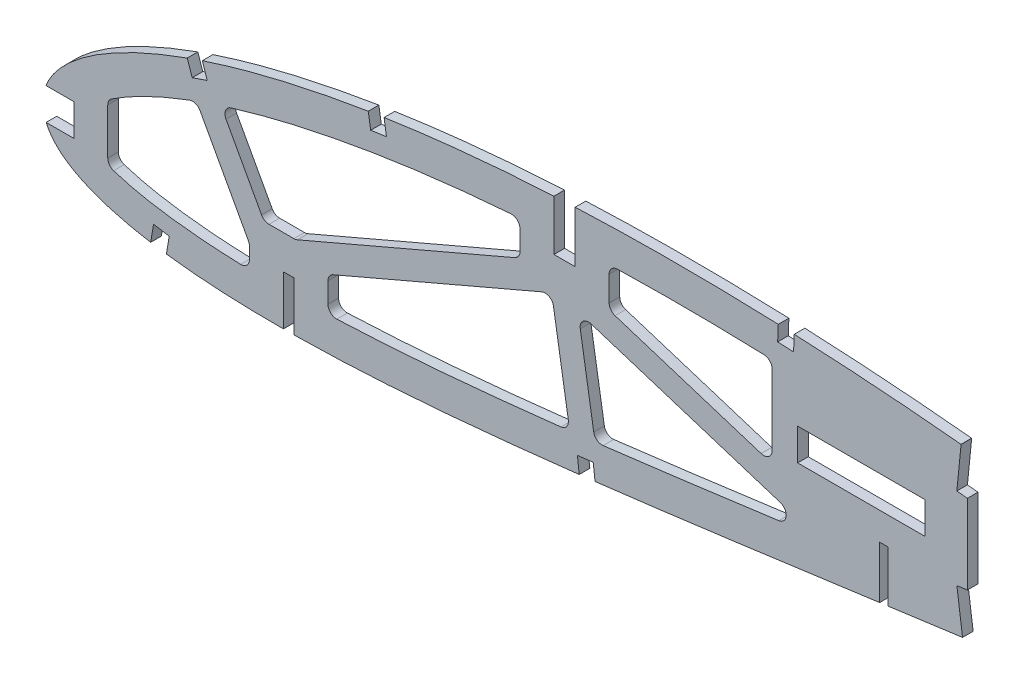
SolidWorks part; units mm, degrees
material "Plywood"
ref_plane "Front Plane" through (0, 0, 0) normal (0, 0, 1) x (1, 0, 0)
ref_plane "Top Plane" through (0, 0, 0) normal (0, 1, 0) x (1, 0, 0)
ref_plane "Right Plane" through (0, 0, 0) normal (1, 0, 0) x (0, 0, -1)
curve "Curve1"
  spline degree 3 poles (452.1031, 0.7048, 0) (452.0685, 0.7262, 0) (451.9301, 0.8117, 0) (451.6183, 1.003, 0) (451.099, 1.3216, 0) (450.372, 1.7653, 0) (449.438, 2.3329, 0) (448.2963, 3.0204, 0) (446.9478, 3.8257, 0) (445.3928, 4.7448, 0) (443.6314, 5.7736, 0) (441.6643, 6.9077, 0) (439.4916, 8.1409, 0) (437.1143, 9.468, 0) (434.5331, 10.8828, 0) (431.7485, 12.3789, 0) (428.7615, 13.9486, 0) (425.5733, 15.5853, 0) (422.1844, 17.2798, 0) (418.5964, 19.0251, 0) (414.8106, 20.8125, 0) (410.8282, 22.6325, 0) (406.6515, 24.4776, 0) (402.2816, 26.3365, 0) (397.7212, 28.201, 0) (392.972, 30.0605, 0) (388.0369, 31.9065, 0) (382.9178, 33.7272, 0) (377.6186, 35.5144, 0) (372.1418, 37.2567, 0) (366.4913, 38.9446, 0) (360.6704, 40.5671, 0) (354.684, 42.1159, 0) (348.5359, 43.5797, 0) (342.2312, 44.9487, 0) (335.775, 46.2147, 0) (329.1727, 47.3651, 0) (322.4425, 48.3989, 0) (315.6929, 49.2588, 0) (308.9571, 50.1023, 0) (302.2314, 50.8946, 0) (295.4235, 51.6533, 0) (288.5399, 52.3742, 0) (281.5875, 53.055, 0) (274.5733, 53.6928, 0) (267.5046, 54.2857, 0) (260.3883, 54.8303, 0) (253.2318, 55.3259, 0) (246.0422, 55.768, 0) (238.8272, 56.1563, 0) (231.5941, 56.4881, 0) (224.3504, 56.7611, 0) (217.1039, 56.9737, 0) (209.862, 57.1238, 0) (202.6326, 57.2105, 0) (195.4232, 57.2315, 0) (188.2416, 57.1863, 0) (181.0954, 57.0734, 0) (173.9924, 56.8912, 0) (166.9401, 56.6395, 0) (159.9462, 56.3182, 0) (153.0184, 55.9248, 0) (146.164, 55.4618, 0) (139.3909, 54.9271, 0) (132.7063, 54.3206, 0) (126.1174, 53.645, 0) (119.6314, 52.8983, 0) (113.2554, 52.0826, 0) (106.9962, 51.1996, 0) (100.8609, 50.2488, 0) (94.8561, 49.2329, 0) (88.9882, 48.153, 0) (83.2635, 47.0122, 0) (77.6882, 45.8109, 0) (72.2682, 44.5525, 0) (67.0092, 43.2395, 0) (61.9167, 41.874, 0) (56.9959, 40.4594, 0) (52.2519, 38.999, 0) (47.6902, 37.4943, 0) (43.3141, 35.951, 0) (39.1291, 34.3702, 0) (35.1384, 32.7568, 0) (31.3466, 31.113, 0) (27.7567, 29.4439, 0) (24.3726, 27.7512, 0) (21.1967, 26.0397, 0) (18.2324, 24.3122, 0) (15.4823, 22.5717, 0) (12.9477, 20.8227, 0) (10.632, 19.0664, 0) (8.5361, 17.307, 0) (6.6613, 15.5474, 0) (5.0102, 13.7886, 0) (3.5829, 12.0339, 0) (2.3811, 10.2847, 0) (1.4051, 8.5424, 0) (0.6571, 6.8085, 0) (0.1363, 5.084, 0) (-0.1488, 3.3712, 0) (-0.2197, 1.669, 0) (-0.0731, 0.5555, 0) (0, 0, 0) knots 0 0 0 0 0.000254 0.001015 0.002283 0.004057 0.006331 0.009105 0.012374 0.016134 0.02038 0.025106 0.030306 0.035972 0.0421 0.048678 0.055702 0.06316 0.071046 0.07935 0.088063 0.097176 0.106678 0.116562 0.126814 0.137428 0.148394 0.1597 0.171338 0.183298 0.19557 0.208144 0.221012 0.234162 0.247587 0.261277 0.275223 0.289414 0.303771 0.317689 0.331784 0.34604 0.360444 0.374983 0.38964 0.404403 0.419257 0.434187 0.449177 0.464215 0.479284 0.49437 0.509458 0.524532 0.539579 0.554583 0.56953 0.584403 0.599191 0.613877 0.628447 0.642889 0.657186 0.671326 0.685294 0.699078 0.712665 0.726043 0.739198 0.752118 0.764792 0.777208 0.789356 0.801224 0.812804 0.824083 0.835055 0.84571 0.856038 0.866034 0.875689 0.884998 0.893953 0.902553 0.910789 0.918661 0.926166 0.933303 0.940071 0.946475 0.952518 0.958205 0.963547 0.968557 0.97325 0.977651 0.981787 0.985694 0.989415 0.993001 0.996508 1 1 1 1
curve "Curve2"
  spline degree 3 poles (0, 0, 0) (0.1161, -0.5481, 0) (0.3488, -1.6467, 0) (0.9811, -3.2283, 0) (1.8173, -4.7487, 0) (2.8749, -6.2038, 0) (4.147, -7.5932, 0) (5.6306, -8.9184, 0) (7.3243, -10.1787, 0) (9.226, -11.3735, 0) (11.3328, -12.5041, 0) (13.6425, -13.5697, 0) (16.1528, -14.5701, 0) (18.8611, -15.5039, 0) (21.764, -16.3724, 0) (24.8588, -17.1737, 0) (28.1419, -17.9088, 0) (31.6103, -18.5759, 0) (35.26, -19.1755, 0) (39.0874, -19.7075, 0) (43.0885, -20.172, 0) (47.2594, -20.5682, 0) (51.596, -20.8969, 0) (56.0938, -21.1583, 0) (60.7487, -21.3533, 0) (65.556, -21.481, 0) (70.5112, -21.5436, 0) (75.6096, -21.5419, 0) (80.8464, -21.4754, 0) (86.2171, -21.3479, 0) (91.7164, -21.1586, 0) (97.3395, -20.9096, 0) (103.0813, -20.6036, 0) (108.9365, -20.2416, 0) (114.9002, -19.8251, 0) (120.967, -19.3576, 0) (127.1315, -18.8401, 0) (133.3883, -18.2757, 0) (139.7319, -17.6673, 0) (146.1567, -17.0167, 0) (152.6572, -16.327, 0) (159.2275, -15.6004, 0) (165.862, -14.8409, 0) (172.5546, -14.0497, 0) (179.2998, -13.2315, 0) (186.0911, -12.3877, 0) (192.923, -11.5217, 0) (199.7891, -10.6375, 0) (206.6832, -9.7349, 0) (213.5994, -8.8205, 0) (220.5311, -7.8935, 0) (227.4721, -6.9586, 0) (234.4161, -6.0188, 0) (241.3564, -5.0743, 0) (248.2868, -4.1291, 0) (255.2009, -3.1857, 0) (262.0918, -2.2442, 0) (268.9535, -1.3094, 0) (275.779, -0.3811, 0) (282.5619, 0.5389, 0) (289.2958, 1.4477, 0) (295.9744, 2.3443, 0) (302.5907, 3.228, 0) (309.138, 4.0992, 0) (315.5119, 4.9314, 0) (321.6955, 5.769, 0) (327.7099, 6.4556, 0) (333.6493, 7.0417, 0) (339.52, 7.5222, 0) (345.315, 7.9041, 0) (351.0275, 8.19, 0) (356.6509, 8.3839, 0) (362.1779, 8.4917, 0) (367.6017, 8.516, 0) (372.9148, 8.4647, 0) (378.1105, 8.3417, 0) (383.1813, 8.1528, 0) (388.1203, 7.9042, 0) (392.9205, 7.6027, 0) (397.5745, 7.2527, 0) (402.076, 6.8625, 0) (406.4179, 6.4377, 0) (410.5937, 5.9833, 0) (414.5972, 5.5086, 0) (418.4221, 5.0169, 0) (422.0625, 4.5163, 0) (425.5126, 4.0117, 0) (428.7669, 3.5097, 0) (431.8204, 3.015, 0) (434.6681, 2.5342, 0) (437.3055, 2.0718, 0) (439.7281, 1.6323, 0) (441.9324, 1.2212, 0) (443.9143, 0.8406, 0) (445.6709, 0.4968, 0) (447.199, 0.1913, 0) (448.4964, -0.0716, 0) (449.5609, -0.2909, 0) (450.3908, -0.463, 0) (450.9844, -0.5881, 0) (451.3411, -0.6626, 0) (451.4997, -0.6964, 0) (451.5393, -0.7048, 0) knots 0 0 0 0 0.003638 0.007293 0.011028 0.014901 0.018963 0.023258 0.027821 0.032679 0.037853 0.043362 0.049215 0.055422 0.061989 0.068918 0.076211 0.083868 0.091887 0.100266 0.109 0.118085 0.127515 0.137285 0.147388 0.157816 0.168563 0.179619 0.190977 0.202627 0.21456 0.226767 0.239236 0.251959 0.264924 0.27812 0.291536 0.30516 0.318981 0.332985 0.347163 0.361499 0.375981 0.390597 0.405333 0.420175 0.43511 0.450124 0.465203 0.480333 0.495501 0.51069 0.525887 0.541078 0.556247 0.571382 0.586466 0.601485 0.616424 0.631269 0.646007 0.660621 0.675098 0.689423 0.703582 0.716908 0.730009 0.742952 0.755726 0.76832 0.780724 0.792927 0.804916 0.816679 0.828204 0.839475 0.850481 0.861208 0.871639 0.881763 0.891564 0.901027 0.910139 0.918884 0.927249 0.935221 0.942785 0.949928 0.956638 0.962904 0.968712 0.974054 0.978918 0.983297 0.98718 0.990561 0.993433 0.995791 0.99763 0.998946 0.999737 1 1 1 1
sketch "Sketch1" plane through (0, 0, 0) normal (0, 0, 1) x (1, 0, 0)
  line L24 (435.3301, 0.6787) -> (439.1729, -1.6142)
  line L25 (434.7872, -0.6787) -> (439.1729, -1.6142)
  spline S4 degree 3 poles (0, 0) (0.1118, -0.5277) (0.3359, -1.5856) (0.9447, -3.1085) (1.7499, -4.5725) (2.7683, -5.9736) (3.9931, -7.3115) (5.4217, -8.5876) (7.0526, -9.8011) (8.8837, -10.9516) (10.9124, -12.0402) (13.1363, -13.0663) (15.5535, -14.0296) (18.1613, -14.9287) (20.9565, -15.765) (23.9365, -16.5366) (27.0978, -17.2444) (30.4375, -17.8867) (33.9519, -18.4641) (37.6373, -18.9763) (41.49, -19.4236) (45.5061, -19.8051) (49.6818, -20.1216) (54.0128, -20.3734) (58.4949, -20.5611) (63.1239, -20.6841) (67.8952, -20.7443) (72.8045, -20.7427) (77.847, -20.6787) (83.0184, -20.5559) (88.3137, -20.3736) (93.7282, -20.1339) (99.2569, -19.8392) (104.895, -19.4906) (110.6374, -19.0896) (116.4791, -18.6394) (122.4149, -18.1411) (128.4396, -17.5977) (134.5478, -17.0118) (140.7343, -16.3853) (146.9936, -15.7212) (153.3201, -15.0216) (159.7085, -14.2903) (166.1528, -13.5285) (172.6478, -12.7406) (179.1872, -11.9281) (185.7655, -11.0942) (192.377, -10.2428) (199.0153, -9.3738) (205.6749, -8.4933) (212.3494, -7.6007) (219.0329, -6.7005) (225.7193, -5.7955) (232.4021, -4.886) (239.0753, -3.9759) (245.7329, -3.0675) (252.3682, -2.161) (258.9753, -1.2608) (265.5476, -0.3669) (272.0789, 0.5189) (278.563, 1.394) (284.9937, 2.2573) (291.3645, 3.1082) (297.669, 3.9471) (303.8064, 4.7484) (309.7606, 5.555) (315.5518, 6.2161) (321.2709, 6.7805) (326.9238, 7.2431) (332.5038, 7.6108) (338.0044, 7.8861) (343.4191, 8.0729) (348.7411, 8.1767) (353.9637, 8.2001) (359.0797, 8.1506) (364.0826, 8.0323) (368.9653, 7.8503) (373.7211, 7.6109) (378.3431, 7.3206) (382.8245, 6.9836) (387.159, 6.6079) (391.3398, 6.1989) (395.3607, 5.7613) (399.2157, 5.3043) (402.8986, 4.8308) (406.404, 4.3487) (409.7261, 3.8629) (412.8597, 3.3795) (415.7999, 2.9031) (418.5419, 2.4402) (421.0815, 1.9949) (423.4142, 1.5717) (425.5368, 1.1759) (427.445, 0.8095) (429.1365, 0.4784) (430.6079, 0.1842) (431.8572, -0.0689) (432.8822, -0.2801) (433.6813, -0.4458) (434.2529, -0.5663) (434.5964, -0.638) (434.749, -0.6706) (434.7872, -0.6787) knots 0 0 0 0 0.003638 0.007293 0.011028 0.014901 0.018963 0.023258 0.027821 0.032679 0.037853 0.043362 0.049215 0.055422 0.061989 0.068918 0.076211 0.083868 0.091887 0.100266 0.109 0.118085 0.127515 0.137285 0.147388 0.157816 0.168563 0.179619 0.190977 0.202627 0.21456 0.226767 0.239236 0.251959 0.264924 0.27812 0.291536 0.30516 0.318981 0.332985 0.347163 0.361499 0.375981 0.390597 0.405333 0.420175 0.43511 0.450124 0.465203 0.480333 0.495501 0.51069 0.525887 0.541078 0.556247 0.571382 0.586466 0.601485 0.616424 0.631269 0.646007 0.660621 0.675098 0.689423 0.703582 0.716908 0.730009 0.742952 0.755726 0.76832 0.780724 0.792927 0.804916 0.816679 0.828204 0.839475 0.850481 0.861208 0.871639 0.881763 0.891564 0.901027 0.910139 0.918884 0.927249 0.935221 0.942785 0.949928 0.956638 0.962904 0.968712 0.974054 0.978918 0.983297 0.98718 0.990561 0.993433 0.995791 0.99763 0.998946 0.999737 1 1 1 1
  spline S5 degree 3 poles (435.3301, 0.6787) (435.2968, 0.6993) (435.1635, 0.7816) (434.8632, 0.9658) (434.3632, 1.2726) (433.6632, 1.6998) (432.7638, 2.2463) (431.6645, 2.9084) (430.3661, 3.6837) (428.8687, 4.5688) (427.1727, 5.5594) (425.2785, 6.6514) (423.1865, 7.8389) (420.8974, 9.1168) (418.4119, 10.4791) (415.7306, 11.9197) (412.8545, 13.4311) (409.7845, 15.0071) (406.5213, 16.6387) (403.0665, 18.3192) (399.4211, 20.0403) (395.5865, 21.7928) (391.5647, 23.5695) (387.357, 25.3594) (382.9657, 27.1547) (378.3927, 28.9452) (373.6407, 30.7228) (368.7116, 32.4759) (363.609, 34.1968) (358.3353, 35.8745) (352.8945, 37.4998) (347.2896, 39.0621) (341.5252, 40.5534) (335.6052, 41.9629) (329.5344, 43.2811) (323.3177, 44.5002) (316.9603, 45.6079) (310.4799, 46.6033) (303.9807, 47.4313) (297.4948, 48.2435) (291.0186, 49.0064) (284.4633, 49.737) (277.8351, 50.4311) (271.1406, 51.0867) (264.3866, 51.7008) (257.5802, 52.2717) (250.7279, 52.7961) (243.8369, 53.2733) (236.914, 53.699) (229.9667, 54.0729) (223.0019, 54.3924) (216.027, 54.6553) (209.0493, 54.86) (202.0761, 55.0045) (195.1149, 55.088) (188.173, 55.1082) (181.2578, 55.0647) (174.3767, 54.956) (167.5373, 54.7806) (160.7467, 54.5381) (154.0122, 54.2288) (147.3414, 53.85) (140.7414, 53.4041) (134.2195, 52.8893) (127.7829, 52.3053) (121.4385, 51.6548) (115.1931, 50.9357) (109.0536, 50.1503) (103.0266, 49.3001) (97.119, 48.3846) (91.3369, 47.4064) (85.6868, 46.3665) (80.1745, 45.2681) (74.806, 44.1113) (69.5871, 42.8996) (64.5231, 41.6353) (59.6196, 40.3205) (54.8814, 38.9584) (50.3134, 37.5521) (45.9209, 36.1032) (41.7071, 34.6172) (37.6774, 33.0951) (33.8348, 31.5415) (30.1837, 29.9587) (26.7269, 28.3515) (23.4684, 26.7216) (20.4104, 25.0737) (17.5559, 23.4102) (14.9079, 21.7343) (12.4673, 20.0502) (10.2376, 18.359) (8.2194, 16.6649) (6.4142, 14.9706) (4.8244, 13.2771) (3.45, 11.5875) (2.2928, 9.9031) (1.353, 8.2255) (0.6327, 6.5559) (0.1312, 4.8953) (-0.1433, 3.2462) (-0.2116, 1.607) (-0.0704, 0.5349) (0, 0) knots 0 0 0 0 0.000254 0.001015 0.002283 0.004057 0.006331 0.009105 0.012374 0.016134 0.02038 0.025106 0.030306 0.035972 0.0421 0.048678 0.055702 0.06316 0.071046 0.07935 0.088063 0.097176 0.106678 0.116562 0.126814 0.137428 0.148394 0.1597 0.171338 0.183298 0.19557 0.208144 0.221012 0.234162 0.247587 0.261277 0.275223 0.289414 0.303771 0.317689 0.331784 0.34604 0.360444 0.374983 0.38964 0.404403 0.419257 0.434187 0.449177 0.464215 0.479284 0.49437 0.509458 0.524532 0.539579 0.554583 0.56953 0.584403 0.599191 0.613877 0.628447 0.642889 0.657186 0.671326 0.685294 0.699078 0.712665 0.726043 0.739198 0.752118 0.764792 0.777208 0.789356 0.801224 0.812804 0.824083 0.835055 0.84571 0.856038 0.866034 0.875689 0.884998 0.893953 0.902553 0.910789 0.918661 0.926166 0.933303 0.940071 0.946475 0.952518 0.958205 0.963547 0.968557 0.97325 0.977651 0.981787 0.985694 0.989415 0.993001 0.996508 1 1 1 1
extrude "Boss-Extrude1" add sketch "Sketch1" along normal blind 3.175
sketch "Sketch2" plane through (0, 0, 0) normal (0, 0, -1) x (-1, 0, 0)
  line L0 (-252.7944, 13.2215) -> (-250.2544, 13.2215)
  line L1 (-250.2544, -2.1152) -> (-250.2544, -3.9863)
  line L2 (-252.7944, 13.2215) -> (-252.7944, -2.1152)
  line L4 (-250.2544, -3.9863) -> (-252.7944, -3.0508)
  line L5 (-252.7944, -3.0508) -> (-252.7944, -2.1152)
  line L7 (-159.1319, 54.4222) -> (-159.1319, 39.0391)
  line L8 (-159.1319, 39.0391) -> (-152.7819, 39.0391)
  line L9 (-152.7819, 54.4222) -> (-152.7819, 57.6454)
  line L10 (-74.9944, -5.9288) -> (-74.9944, -20.1418)
  line L12 (-152.7819, 57.6454) -> (-159.1319, 55.5409)
  line L13 (-159.1319, 55.5409) -> (-159.1319, 54.4222)
  line L14 (-71.8194, -5.9288) -> (-71.8194, -20.1418)
  line L16 (-74.9944, -5.9288) -> (-71.8194, -5.9288)
  line L17 (-71.8194, -20.1418) -> (-71.8194, -22.1459)
  line L19 (-152.7819, 54.4222) -> (-152.7819, 39.0391)
  line L20 (-71.8194, -22.1459) -> (-74.9944, -20.9764)
  line L21 (-74.9944, -20.9764) -> (-74.9944, -20.1418)
  line L22 (-250.2544, 13.2215) -> (-250.2544, -2.1152)
extrude "Cut-Extrude1" cut sketch "Sketch2" against normal blind 7.62
sketch "Sketch3" plane through (0, 0, 0) normal (0, 0, -1) x (-1, 0, 0)
  circle A1 centre (-292.3838, 26.2554) radius 6.35
extrude "Cut-Extrude2" cut sketch "Sketch3" against normal blind 7.62
sketch "Sketch4" plane through (0, 0, 3.175) normal (0, 0, 1) x (1, 0, 0)
  line L0 (274.6066, 50.6647) -> (273.3497, 38.0281)
  line L1 (274.6066, 50.6647) -> (273.3497, 38.0281)
  line L2 (276.5088, 37.7139) -> (277.7874, 50.3428)
  line L3 (276.5088, 37.7139) -> (277.7874, 50.3428)
  line L4 (278.2022, 1.3477) -> (276.5088, 13.9346)
  line L5 (278.2022, 1.3477) -> (276.5088, 13.9346)
  line L6 (273.3622, 13.5108) -> (275.0576, 0.9245)
  line L7 (273.3622, 13.5108) -> (275.0576, 0.9245)
  line L8 (224.4836, 49.6431) -> (224.6991, 54.396)
  line L9 (224.4836, 49.6431) -> (224.6991, 54.396)
  line L10 (165.0827, -13.6872) -> (164.5226, -8.9534)
  line L11 (165.0827, -13.6872) -> (164.5226, -8.9534)
  line L12 (102.6454, 44.5104) -> (101.9324, 49.2278)
  line L13 (102.6454, 44.5104) -> (101.9324, 49.2278)
  line L14 (36.8388, -18.5812) -> (37.6418, -13.8082)
  line L15 (36.8388, -18.5812) -> (37.6418, -13.8082)
  line L16 (49.0205, 32.2539) -> (47.492, 36.7462)
  line L17 (49.0205, 32.2539) -> (47.492, 36.7462)
  line L18 (9.0835, -2.7147) -> (9.0835, 6.8103)
  line L19 (9.0835, -2.7147) -> (9.0835, 6.8103)
  line L20 (-0.4415, 6.8103) -> (9.0835, 6.8103)
  line L21 (-0.4415, 6.8103) -> (9.0835, 6.8103)
  line L22 (32.9524, -13.0236) -> (32.1659, -17.7312)
  line L23 (32.9524, -13.0236) -> (32.1659, -17.7312)
  line L24 (97.1897, 48.4826) -> (97.9364, 43.7986)
  line L25 (97.1897, 48.4826) -> (97.9364, 43.7986)
  line L26 (159.7931, -9.5131) -> (160.3442, -14.2455)
  line L27 (159.7931, -9.5131) -> (160.3442, -14.2455)
  line L28 (42.9896, 35.1929) -> (44.512, 30.7197)
  line L29 (42.9896, 35.1929) -> (44.512, 30.7197)
  line L30 (-0.4415, -2.7147) -> (9.0835, -2.7147)
  line L31 (-0.4415, -2.7147) -> (9.0835, -2.7147)
  line L32 (219.9134, 54.5992) -> (219.7258, 49.8498)
  line L33 (219.9134, 54.5992) -> (219.7258, 49.8498)
  line L34 (276.5088, 13.9346) -> (276.5088, 37.7139)
  line L35 (273.3497, 38.0281) -> (276.5088, 37.7139)
  line L36 (276.5088, 13.9346) -> (273.3622, 13.5108)
  line L37 (275.0576, 0.9245) -> (278.2022, 1.3477)
  line L38 (219.7258, 49.8498) -> (224.4836, 49.6431)
  line L39 (224.6991, 54.396) -> (219.9134, 54.5992)
  line L40 (159.7931, -9.5131) -> (164.5226, -8.9534)
  line L41 (165.0827, -13.6872) -> (160.3442, -14.2455)
  line L42 (42.9896, 35.1929) -> (47.492, 36.7462)
  line L43 (44.512, 30.7197) -> (49.0205, 32.2539)
  line L44 (97.1897, 48.4826) -> (101.9324, 49.2278)
  line L45 (102.6454, 44.5104) -> (97.9364, 43.7986)
  line L46 (-0.4415, 6.8103) -> (-0.4415, -2.7147)
  line L47 (32.9524, -13.0236) -> (37.6418, -13.8082)
  line L48 (36.8388, -18.5812) -> (32.1659, -17.7312)
  line L49 (277.7874, 50.3428) -> (274.6066, 50.6647)
  line L50 (275.0576, 0.9245) -> (275.0576, -18.8331)
  line L51 (225.7088, 31.0179) -> (263.8088, 31.0179)
  line L52 (225.7088, 31.0179) -> (225.7088, 21.4929)
  line L53 (225.7088, 21.4929) -> (263.8088, 21.4929)
  line L54 (263.8088, 31.0179) -> (263.8088, 21.4929)
  line L55 (446.0862, 59.9441) -> (446.0862, -18.8331)
  line L56 (446.0862, -18.8331) -> (275.0576, -18.8331)
  line L57 (274.6066, 50.6647) -> (274.6066, 59.9441)
  line L58 (274.6066, 59.9441) -> (446.0862, 59.9441)
  line L59 (32.1659, -17.7312) -> (31.5691, -21.3035)
  line L60 (31.5691, -21.3035) -> (36.2028, -22.0776)
  line L61 (36.2028, -22.0776) -> (36.8388, -18.5812)
  circle A0 centre (292.3838, 26.2554) radius 6.35 construction
  circle A1 centre (292.3838, 26.2554) radius 6.35
  point P40 (263.8088, 26.2554)
  dimension "D1" = 9.525
  dimension "D2" = 38.1
  dimension "D3" = 12.7
extrude "Cut-Extrude3" cut sketch "Sketch4" against normal through all contours L31 L19 L21 | L29 L43 L17 | L48 L15 L47 L23 | L45 L13 L25 | L40 L27 L11 | L33 L38 L9 | L54 L51 L52 L53 | L3 L49 L1 L35 | L3 L34 L5 | L7 L37 L5 L36 | L60 L61 L59 | L61 L48 L59 region at (275.5637, 44.1947, 3.175) region at (361.7755, 20.4803, 3.175) region at (275.7826, 7.4301, 3.175) region at (222.206, 52.1243, 3.175) region at (162.4359, -11.6005, 3.175) region at (99.9278, 46.5083, 3.175) region at (34.9052, -15.7866, 3.175) region at (34.1874, -19.9188, 3.175) region at (46.0051, 33.7288, 3.175) region at (4.321, 2.0478, 3.175) region at (244.7588, 26.2554, 3.175)
sketch "Sketch5" plane through (0, 0, 3.175) normal (0, 0, 1) x (1, 0, 0)
  line L0 (0.7643, 6.8103) -> (9.0835, 6.8103) construction
  line L1 (0.7643, 6.8103) -> (9.0835, 6.8103) construction
  line L2 (0.803, -2.7147) -> (9.0835, -2.7147) construction
  line L3 (0.803, -2.7147) -> (9.0835, -2.7147) construction
  line L4 (273.3622, 13.5108) -> (275.0576, 0.9245) construction
  line L5 (273.3622, 13.5108) -> (275.0576, 0.9245) construction
  line L6 (274.6066, 50.6647) -> (273.3497, 38.0281) construction
  line L7 (274.6066, 50.6647) -> (273.3497, 38.0281) construction
  line L8 (19.2435, 12.3749) -> (19.2435, -4.5391)
  line L9 (9.0835, -2.7147) -> (9.0835, 6.8103) construction
  line L10 (61.6594, 4.2312) -> (46.7663, 31.4868) construction
  line L11 (44.512, 30.7197) -> (49.0205, 32.2539) construction
  line L12 (85.1544, 4.2312) -> (142.6219, 28.8791) construction
  line L13 (169.2919, 28.8791) -> (240.0944, 6.4173) construction
  line L14 (155.9569, 28.8791) -> (162.1578, -9.2332) construction
  line L15 (159.7931, -9.5131) -> (164.5226, -8.9534) construction
  line L16 (66.0011, 4.2312) -> (50.1097, 33.3137)
  line L17 (85.1544, 0.0856) -> (152.2877, 28.8791)
  line L18 (152.1093, 28.8026) -> (158.3973, -9.8451)
  line L19 (159.9871, 27.8339) -> (238.9423, 2.7857)
  line L20 (61.6594, -3.7144) -> (43.4229, 29.6599)
  line L21 (75.4887, 4.2312) -> (142.6219, 33.0248)
  line L22 (159.7175, 29.4909) -> (165.9184, -8.6214)
  line L23 (169.2919, 32.8762) -> (241.2466, 10.049)
  line L24 (65.0029, 6.0582) -> (50.1097, 33.3137) construction
  line L25 (58.316, 2.4043) -> (43.4229, 29.6599) construction
  line L26 (83.6526, 7.7327) -> (141.1201, 32.3806) construction
  line L27 (86.6562, 0.7297) -> (144.1237, 25.3776) construction
  line L28 (152.1964, 28.2673) -> (158.3973, -9.8451) construction
  line L29 (168.1398, 25.2475) -> (238.9423, 2.7857) construction
  line L30 (170.4441, 32.5107) -> (241.2466, 10.049) construction
  line L35 (85.1544, 4.2312) -> (85.1544, -20.7123)
  line L36 (61.6594, 4.2312) -> (85.1544, 4.2312)
  line L37 (61.6594, -20.7377) -> (61.6594, 4.2312)
  line L38 (85.1544, 4.2312) -> (85.1544, -20.7123)
  line L39 (61.6594, 4.2312) -> (85.1544, 4.2312)
  line L40 (61.6594, -10.4783) -> (61.6594, 4.2312)
  line L46 (240.0944, -2.4499) -> (240.0944, 13.2215)
  line L47 (169.2919, 54.4587) -> (169.2919, 28.8791)
  line L48 (169.2919, 28.8791) -> (142.6219, 28.8791)
  line L49 (142.6219, 28.8791) -> (142.6219, 54.1523)
  line L50 (169.2919, 44.6566) -> (169.2919, 28.8791)
  line L51 (169.2919, 28.8791) -> (142.6219, 28.8791)
  line L52 (142.6219, 28.8791) -> (142.6219, 43.3411)
  line L53 (240.0944, 6.4173) -> (240.0944, 13.8729)
  line L62 (263.8088, 38.6379) -> (218.0888, 38.6379)
  line L63 (218.0888, 38.6379) -> (218.0888, 13.8729)
  line L64 (218.0888, 13.8729) -> (263.8088, 13.8729)
  line L66 (218.0888, 44.4072) -> (218.0888, 13.8729)
  line L67 (218.0888, 13.8729) -> (240.0944, 13.8729)
  spline S4 degree 3 poles (1523.9168, 1677.8723) (459.4041, -20.0575) (448.5517, -7.4305) (434.8632, 0.9658) (434.3632, 1.2726) (433.6632, 1.6998) (432.7638, 2.2463) (431.6645, 2.9084) (430.3661, 3.6837) (428.8687, 4.5688) (427.1727, 5.5594) (425.2785, 6.6514) (423.1865, 7.8389) (420.8974, 9.1168) (418.4119, 10.4791) (415.7306, 11.9197) (412.8545, 13.4311) (409.7845, 15.0071) (406.5213, 16.6387) (403.0665, 18.3192) (399.4211, 20.0403) (395.5865, 21.7928) (391.5647, 23.5695) (387.357, 25.3594) (382.9657, 27.1547) (378.3927, 28.9452) (373.6407, 30.7228) (368.7116, 32.4759) (363.609, 34.1968) (358.3353, 35.8745) (352.8945, 37.4998) (347.2896, 39.0621) (341.5252, 40.5534) (335.6052, 41.9629) (329.5344, 43.2811) (323.3177, 44.5002) (316.9603, 45.6079) (310.4799, 46.6033) (303.9807, 47.4313) (297.4948, 48.2435) (291.0186, 49.0064) (284.4633, 49.737) (277.8351, 50.4311) (271.1406, 51.0867) (264.3866, 51.7008) (257.5802, 52.2717) (250.7279, 52.7961) (243.8369, 53.2733) (236.914, 53.699) (229.9667, 54.0729) (223.0019, 54.3924) (216.027, 54.6553) (209.0493, 54.86) (202.0761, 55.0045) (195.1149, 55.088) (188.173, 55.1082) (181.2578, 55.0647) (174.3767, 54.956) (167.5373, 54.7806) (160.7467, 54.5381) (154.0122, 54.2288) (147.3414, 53.85) (140.7414, 53.4041) (134.2195, 52.8893) (127.7829, 52.3053) (121.4385, 51.6548) (115.1931, 50.9357) (109.0536, 50.1503) (103.0266, 49.3001) (97.119, 48.3846) (91.3369, 47.4064) (85.6868, 46.3665) (80.1745, 45.2681) (74.806, 44.1113) (69.5871, 42.8996) (64.5231, 41.6353) (59.6196, 40.3205) (54.8814, 38.9584) (50.3134, 37.5521) (45.9209, 36.1032) (41.7071, 34.6172) (37.6774, 33.0951) (33.8348, 31.5415) (30.1837, 29.9587) (26.7269, 28.3515) (23.4684, 26.7216) (20.4104, 25.0737) (17.5559, 23.4102) (14.9079, 21.7343) (12.4673, 20.0502) (10.2376, 18.359) (8.2194, 16.6649) (6.4142, 14.9706) (4.8244, 13.2771) (3.45, 11.5875) (2.2928, 9.9031) (1.353, 8.2255) (0.6327, 6.5559) (0.1312, 4.8953) (-0.1433, 3.2462) (-1.0017, -17.3492) (61.8716, -33.4146) (-1991.1542, -180.949) knots -0.101807 -0.101807 -0.101807 -0.101807 0.000254 0.001015 0.002283 0.004057 0.006331 0.009105 0.012374 0.016134 0.02038 0.025106 0.030306 0.035972 0.0421 0.048678 0.055702 0.06316 0.071046 0.07935 0.088063 0.097176 0.106678 0.116562 0.126814 0.137428 0.148394 0.1597 0.171338 0.183298 0.19557 0.208144 0.221012 0.234162 0.247587 0.261277 0.275223 0.289414 0.303771 0.317689 0.331784 0.34604 0.360444 0.374983 0.38964 0.404403 0.419257 0.434187 0.449177 0.464215 0.479284 0.49437 0.509458 0.524532 0.539579 0.554583 0.56953 0.584403 0.599191 0.613877 0.628447 0.642889 0.657186 0.671326 0.685294 0.699078 0.712665 0.726043 0.739198 0.752118 0.764792 0.777208 0.789356 0.801224 0.812804 0.824083 0.835055 0.84571 0.856038 0.866034 0.875689 0.884998 0.893953 0.902553 0.910789 0.918661 0.926166 0.933303 0.940071 0.946475 0.952518 0.958205 0.963547 0.968557 0.97325 0.977651 0.981787 0.985694 0.989415 0.993001 0.996508 1.122415 1.122415 1.122415 1.122415 only from (435.3301, 0.6787) to (0, 0) construction
  spline S7 degree 3 poles (-1938.1568, -491.7767) (47.0927, 52.1326) (-6.7204, 16.0645) (0.9447, -3.1085) (1.7499, -4.5725) (2.7683, -5.9736) (3.9931, -7.3115) (5.4217, -8.5876) (7.0526, -9.8011) (8.8837, -10.9516) (10.9124, -12.0402) (13.1363, -13.0663) (15.5535, -14.0296) (18.1613, -14.9287) (20.9565, -15.765) (23.9365, -16.5366) (27.0978, -17.2444) (30.4375, -17.8867) (33.9519, -18.4641) (37.6373, -18.9763) (41.49, -19.4236) (45.5061, -19.8051) (49.6818, -20.1216) (54.0128, -20.3734) (58.4949, -20.5611) (63.1239, -20.6841) (67.8952, -20.7443) (72.8045, -20.7427) (77.847, -20.6787) (83.0184, -20.5559) (88.3137, -20.3736) (93.7282, -20.1339) (99.2569, -19.8392) (104.895, -19.4906) (110.6374, -19.0896) (116.4791, -18.6394) (122.4149, -18.1411) (128.4396, -17.5977) (134.5478, -17.0118) (140.7343, -16.3853) (146.9936, -15.7212) (153.3201, -15.0216) (159.7085, -14.2903) (166.1528, -13.5285) (172.6478, -12.7406) (179.1872, -11.9281) (185.7655, -11.0942) (192.377, -10.2428) (199.0153, -9.3738) (205.6749, -8.4933) (212.3494, -7.6007) (219.0329, -6.7005) (225.7193, -5.7955) (232.4021, -4.886) (239.0753, -3.9759) (245.7329, -3.0675) (252.3682, -2.161) (258.9753, -1.2608) (265.5476, -0.3669) (272.0789, 0.5189) (278.563, 1.394) (284.9937, 2.2573) (291.3645, 3.1082) (297.669, 3.9471) (303.8064, 4.7484) (309.7606, 5.555) (315.5518, 6.2161) (321.2709, 6.7805) (326.9238, 7.2431) (332.5038, 7.6108) (338.0044, 7.8861) (343.4191, 8.0729) (348.7411, 8.1767) (353.9637, 8.2001) (359.0797, 8.1506) (364.0826, 8.0323) (368.9653, 7.8503) (373.7211, 7.6109) (378.3431, 7.3206) (382.8245, 6.9836) (387.159, 6.6079) (391.3398, 6.1989) (395.3607, 5.7613) (399.2157, 5.3043) (402.8986, 4.8308) (406.404, 4.3487) (409.7261, 3.8629) (412.8597, 3.3795) (415.7999, 2.9031) (418.5419, 2.4402) (421.0815, 1.9949) (423.4142, 1.5717) (425.5368, 1.1759) (427.445, 0.8095) (429.1365, 0.4784) (430.6079, 0.1842) (431.8572, -0.0689) (432.8822, -0.2801) (433.6813, -0.4458) (434.2529, -0.5663) (448.3411, -3.5068) (461.0644, -11.9601) (889.5705, 1946.1435) knots -0.127812 -0.127812 -0.127812 -0.127812 0.003638 0.007293 0.011028 0.014901 0.018963 0.023258 0.027821 0.032679 0.037853 0.043362 0.049215 0.055422 0.061989 0.068918 0.076211 0.083868 0.091887 0.100266 0.109 0.118085 0.127515 0.137285 0.147388 0.157816 0.168563 0.179619 0.190977 0.202627 0.21456 0.226767 0.239236 0.251959 0.264924 0.27812 0.291536 0.30516 0.318981 0.332985 0.347163 0.361499 0.375981 0.390597 0.405333 0.420175 0.43511 0.450124 0.465203 0.480333 0.495501 0.51069 0.525887 0.541078 0.556247 0.571382 0.586466 0.601485 0.616424 0.631269 0.646007 0.660621 0.675098 0.689423 0.703582 0.716908 0.730009 0.742952 0.755726 0.76832 0.780724 0.792927 0.804916 0.816679 0.828204 0.839475 0.850481 0.861208 0.871639 0.881763 0.891564 0.901027 0.910139 0.918884 0.927249 0.935221 0.942785 0.949928 0.956638 0.962904 0.968712 0.974054 0.978918 0.983297 0.98718 0.990561 0.993433 0.995791 0.99763 0.998946 0.999737 1.094845 1.094845 1.094845 1.094845 only from (0, 0) to (434.7872, -0.6787) construction
  spline S8 degree 3 poles (0.803, -2.7147) (0.8566, -2.8383) (1.1411, -3.4655) (1.7499, -4.5725) (2.7683, -5.9736) (3.9931, -7.3115) (5.4217, -8.5876) (7.0526, -9.8011) (8.8837, -10.9516) (10.9124, -12.0402) (13.1363, -13.0663) (15.5535, -14.0296) (18.1613, -14.9287) (20.9565, -15.765) (23.9365, -16.5366) (27.0978, -17.2444) (30.4375, -17.8867) (33.9519, -18.4641) (37.6373, -18.9763) (41.49, -19.4236) (45.5061, -19.8051) (49.6818, -20.1216) (54.0128, -20.3734) (58.4949, -20.5611) (63.1239, -20.6841) (67.8952, -20.7443) (72.8045, -20.7427) (77.847, -20.6787) (83.0184, -20.5559) (88.3137, -20.3736) (93.7282, -20.1339) (99.2569, -19.8392) (104.895, -19.4906) (110.6374, -19.0896) (116.4791, -18.6394) (122.4149, -18.1411) (128.4396, -17.5977) (134.5478, -17.0118) (140.7343, -16.3853) (146.9936, -15.7212) (153.3201, -15.0216) (159.7085, -14.2903) (166.1528, -13.5285) (172.6478, -12.7406) (179.1872, -11.9281) (185.7655, -11.0942) (192.377, -10.2428) (199.0153, -9.3738) (205.6749, -8.4933) (212.3494, -7.6007) (219.0329, -6.7005) (225.7193, -5.7955) (232.4021, -4.886) (239.0753, -3.9759) (245.7329, -3.0675) (252.3682, -2.161) (258.9753, -1.2608) (265.5476, -0.3669) (270.9047, 0.3596) (274.0703, 0.7875) (275.0581, 0.9208) knots 0.006385 0.006385 0.006385 0.006385 0.007293 0.011028 0.014901 0.018963 0.023258 0.027821 0.032679 0.037853 0.043362 0.049215 0.055422 0.061989 0.068918 0.076211 0.083868 0.091887 0.100266 0.109 0.118085 0.127515 0.137285 0.147388 0.157816 0.168563 0.179619 0.190977 0.202627 0.21456 0.226767 0.239236 0.251959 0.264924 0.27812 0.291536 0.30516 0.318981 0.332985 0.347163 0.361499 0.375981 0.390597 0.405333 0.420175 0.43511 0.450124 0.465203 0.480333 0.495501 0.51069 0.525887 0.541078 0.556247 0.571382 0.586466 0.601485 0.616424 0.631269 0.638002 0.638002 0.638002 0.638002 construction
  spline S9 degree 3 poles (274.6145, 50.7446) (273.4626, 50.8575) (270.0595, 51.185) (264.3866, 51.7008) (257.5802, 52.2717) (250.7279, 52.7961) (243.8369, 53.2733) (236.914, 53.699) (229.9667, 54.0729) (223.0019, 54.3924) (216.027, 54.6553) (209.0493, 54.86) (202.0761, 55.0045) (195.1149, 55.088) (188.173, 55.1082) (181.2578, 55.0647) (174.3767, 54.956) (167.5373, 54.7806) (160.7467, 54.5381) (154.0122, 54.2288) (147.3414, 53.85) (140.7414, 53.4041) (134.2195, 52.8893) (127.7829, 52.3053) (121.4385, 51.6548) (115.1931, 50.9357) (109.0536, 50.1503) (103.0266, 49.3001) (97.119, 48.3846) (91.3369, 47.4064) (85.6868, 46.3665) (80.1745, 45.2681) (74.806, 44.1113) (69.5871, 42.8996) (64.5231, 41.6353) (59.6196, 40.3205) (54.8814, 38.9584) (50.3134, 37.5521) (45.9209, 36.1032) (41.7071, 34.6172) (37.6774, 33.0951) (33.8348, 31.5415) (30.1837, 29.9587) (26.7269, 28.3515) (23.4684, 26.7216) (20.4104, 25.0737) (17.5559, 23.4102) (14.9079, 21.7343) (12.4673, 20.0502) (10.2376, 18.359) (8.2194, 16.6649) (6.4142, 14.9706) (4.8244, 13.2771) (3.45, 11.5875) (2.2928, 9.9031) (1.404, 8.3167) (0.9441, 7.2755) (0.7643, 6.8103) knots 0.36748 0.36748 0.36748 0.36748 0.374983 0.38964 0.404403 0.419257 0.434187 0.449177 0.464215 0.479284 0.49437 0.509458 0.524532 0.539579 0.554583 0.56953 0.584403 0.599191 0.613877 0.628447 0.642889 0.657186 0.671326 0.685294 0.699078 0.712665 0.726043 0.739198 0.752118 0.764792 0.777208 0.789356 0.801224 0.812804 0.824083 0.835055 0.84571 0.856038 0.866034 0.875689 0.884998 0.893953 0.902553 0.910789 0.918661 0.926166 0.933303 0.940071 0.946475 0.952518 0.958205 0.963547 0.968557 0.97325 0.977651 0.981787 0.985018 0.985018 0.985018 0.985018 construction
  spline S10 degree 1 poles (273.6234, 40.633) (10.241, 3.1473) knots 0 0 1 1 construction
  spline S11 degree 3 poles (273.6234, 40.633) (261.8996, 41.7822) (246.3218, 43.0254) (224.858, 44.1754) (212.2098, 44.6377) (195.2259, 44.9816) (179.6649, 44.9617) (164.4565, 44.5306) (154.8005, 44.0998) (146.6761, 43.6349) (139.351, 43.1141) (128.8047, 42.2286) (115.3869, 40.8171) (98.0892, 38.3586) (80.9736, 35.1878) (66.9367, 31.8567) (55.9177, 28.696) (47.7947, 26.0481) (39.8579, 23.0898) (32.1818, 19.7752) (26.1041, 16.671) (22.151, 14.3095) (20.0018, 12.906) (18.72, 12.0134) (17.1919, 10.8896) (15.2717, 9.3616) (13.3943, 7.5998) (12.0434, 6.07) (11.2157, 4.9715) (10.7011, 4.133) (10.4008, 3.5344) (10.2931, 3.2822) (10.241, 3.1473) knots 0.36748 0.36748 0.36748 0.36748 0.444672 0.469815 0.508411 0.527709 0.581332 0.61065 0.627813 0.644976 0.664275 0.676249 0.714845 0.753441 0.792037 0.830634 0.849932 0.86923 0.888528 0.907826 0.927124 0.936773 0.941413 0.946237 0.94865 0.956071 0.96572 0.970545 0.975369 0.980194 0.982606 0.985018 0.985018 0.985018 0.985018 only from (218.0888, 44.4072) to (19.2435, 12.3749)
  spline S12 degree 1 poles (10.1243, 1.3276) (273.699, 10.9895) knots 0 0 1 1 construction
  spline S13 degree 3 poles (10.1243, 1.3276) (10.1575, 1.251) (10.2303, 1.103) (10.4049, 0.8036) (10.7495, 0.3423) (11.4413, -0.3586) (12.685, -1.3632) (14.6996, -2.6013) (16.8832, -3.6135) (18.675, -4.3336) (19.9239, -4.7918) (22.0966, -5.515) (26.2032, -6.6904) (32.7132, -8.0456) (40.8413, -9.1836) (49.0966, -9.9348) (55.3601, -10.273) (60.2441, -10.4459) (63.1254, -10.5167) (70.9778, -10.6322) (83.1615, -10.477) (100.3763, -9.6617) (117.6379, -8.4001) (140.6921, -6.2673) (169.5492, -2.9697) (201.8108, 1.214) (228.1306, 4.7834) (251.2879, 7.9457) (265.2968, 9.8553) (273.699, 10.9895) knots 0.006385 0.006385 0.006385 0.006385 0.008852 0.011319 0.016254 0.021188 0.026123 0.035992 0.044829 0.047296 0.052231 0.05573 0.065599 0.085337 0.105075 0.124813 0.144188 0.149123 0.158992 0.164289 0.203765 0.243241 0.282717 0.322194 0.401146 0.480098 0.542591 0.580755 0.638002 0.638002 0.638002 0.638002 only from (19.2435, -4.5391) to (240.0944, 6.4173)
  dimension "D3" = 10.16
  dimension "D1" = 10.16
  dimension "D2" = 10.16
  dimension "D4" = 10.16
  dimension "D5" = 10.16
  dimension "D6" = 10.16
  dimension "D7" = 7.62
  dimension "D8" = 3.81
  dimension "D9" = 3.81
extrude "Cut-Extrude4" cut sketch "Sketch5" against normal through all contours L8 S13 L40 L20 S11 | L52 S11 L16 L39 L21 | L38 S13 L18 L17 | L22 S13 L19 | L66 S11 L50 L23 region at (39.6265, 4.8388, 3.175) region at (94.9819, 25.6248, 3.175) region at (126.0755, 4.7732, 3.175) region at (196.8384, 34.4584, 3.175) region at (185.5062, 9.8246, 3.175)
fillet "Fillet1" radius 2.54 21 edges at (169.2919, 32.8762, 1.5875) (169.2919, 44.6566, 1.5875) (218.0888, 44.4072, 1.5875) (218.0888, 17.3957, 1.5875) (19.2435, 12.3749, 1.5875) (45.8148, 25.2824, 1.5875) (61.6594, -3.7144, 1.5875) (19.2435, -4.5391, 1.5875) (85.1544, 0.0856, 1.5875) (152.1093, 28.8026, 1.5875) (157.4976, -4.3152, 1.5875) (85.1544, -10.314, 1.5875) (142.6219, 33.0248, 1.5875) (75.4887, 4.2312, 1.5875) (66.0011, 4.2312, 1.5875) (53.1378, 27.7721, 1.5875) (142.6219, 43.3411, 1.5875) (159.9871, 27.8339, 1.5875) (231.282, 5.2159, 1.5875) (165.0725, -3.4222, 1.5875) (61.6594, -10.4783, 1.5875)
move or copy body "Body-Move/Copy1" [suppressed] bodies to move or copy 118 119 parameters "D1"=0, "D2"=0, "D3"=0
